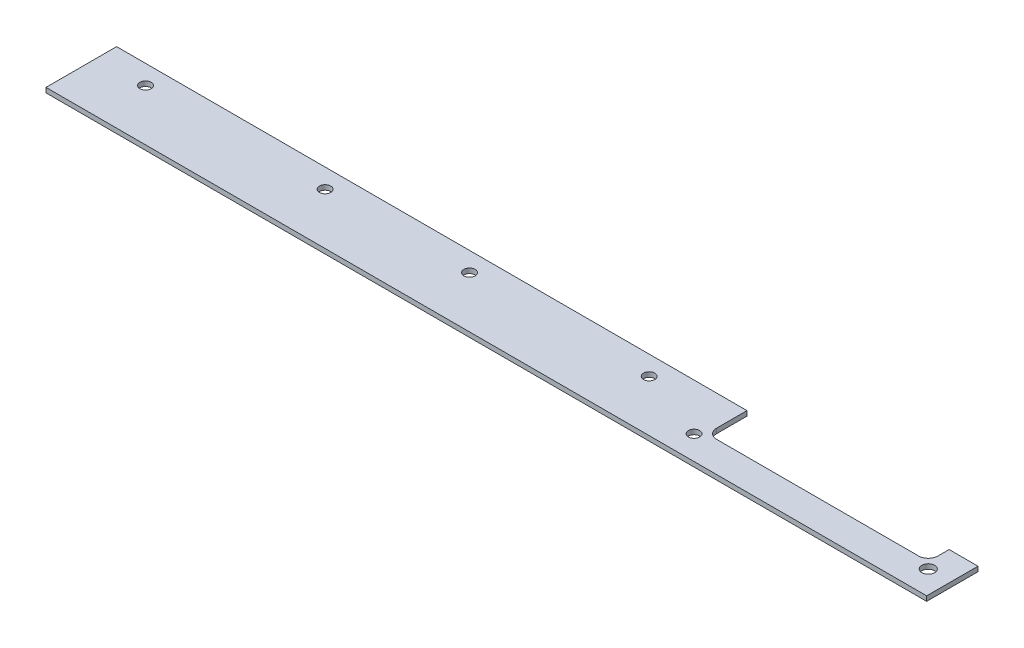
SolidWorks part; units mm, degrees
material "Простая углеродистая сталь"
ref_plane "Спереди" through (0, 0, 0) normal (0, 0, 1) x (1, 0, 0)
ref_plane "Сверху" through (0, 0, 0) normal (0, 1, 0) x (1, 0, 0)
ref_plane "Справа" through (0, 0, 0) normal (1, 0, 0) x (0, 0, -1)
sketch "Эскиз1" plane through (0, 0, 0) normal (0, 1, 0) x (1, 0, 0)
  line L0 (196.5, 22) -> (196.5, 12.5)
  line L1 (0, 0) -> (274.5, 0)
  line L2 (0, 0) -> (0, 22)
  line L3 (0, 22) -> (196.5, 22)
  line L5 (199.5, 9.5) -> (262.5, 9.5)
  line L7 (265.5, 12.5) -> (265.5, 16)
  line L8 (265.5, 16) -> (274.5, 16)
  line L9 (274.5, 16) -> (274.5, 0)
  circle A1 centre (194.5, 7.5) radius 1.75
  circle A2 centre (71, 16) radius 1.75
  circle A3 centre (15, 16) radius 1.75
  circle A4 centre (116, 16) radius 1.75
  circle A5 centre (172, 16) radius 1.75
  circle A8 centre (267.5, 7.5) radius 2
  arc A9 (196.5, 12.5) -> (199.5, 9.5) centre (199.5, 12.5) ccw
  arc A10 (262.5, 9.5) -> (265.5, 12.5) centre (262.5, 12.5) ccw
  point P17 (0, 0)
  dimension "D2" = 3
  dimension "D3" = 3
  dimension "D1" = 2
extrude "Бобышка-Вытянуть1" add sketch "Эскиз1" along normal blind 1.5
